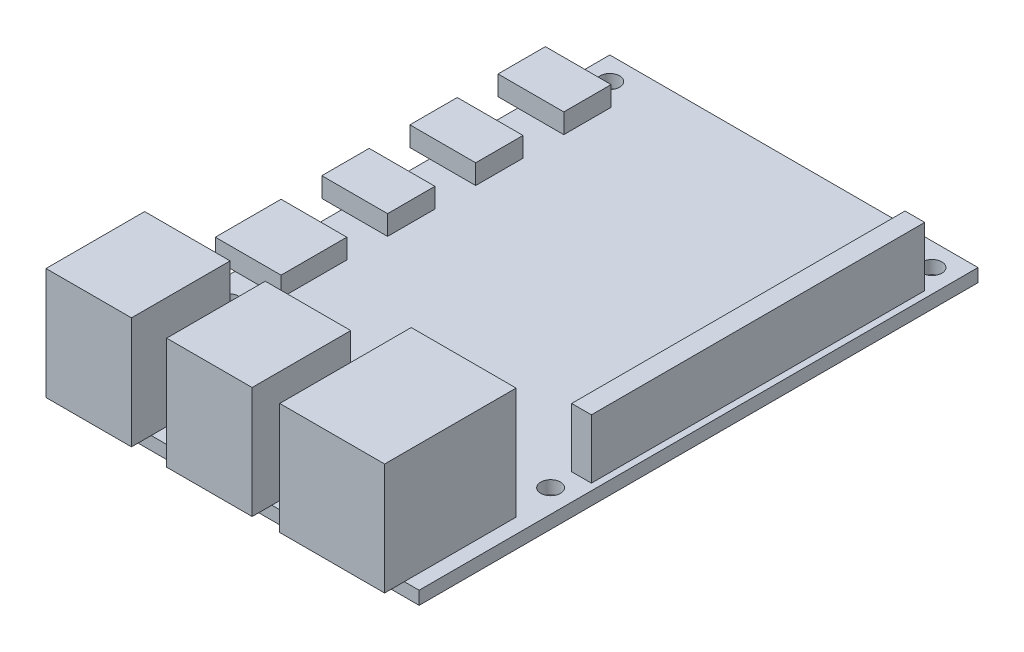
SolidWorks part; units mm, degrees
ref_plane "Front Plane" through (0, 0, 0) normal (0, 0, 1) x (1, 0, 0)
ref_plane "Top Plane" through (0, 0, 0) normal (0, 1, 0) x (1, 0, 0)
ref_plane "Right Plane" through (0, 0, 0) normal (1, 0, 0) x (0, 0, -1)
sketch "Sketch1" plane through (0, 0, 0) normal (0, 1, 0) x (1, 0, 0)
  line L1 (-28, -42.5) -> (28, -42.5)
  line L2 (-28, -42.5) -> (-28, 42.5)
  line L3 (-28, 42.5) -> (28, 42.5)
  line L4 (28, -42.5) -> (28, 42.5)
  line L5 (-28, -42.5) -> (28, 42.5) construction
  line L6 (-28, 42.5) -> (28, -42.5) construction
  line L7 (-24.5, 39) -> (24.5, 39) construction
  line L8 (-24.5, 39) -> (-24.5, -19) construction
  line L9 (-24.5, -19) -> (24.5, -19) construction
  line L10 (24.5, 39) -> (24.5, -19) construction
  circle A0 centre (-24.5, 39) radius 1.5
  circle A1 centre (24.5, 39) radius 1.5
  circle A2 centre (-24.5, -19) radius 1.5
  circle A3 centre (24.5, -19) radius 1.5
  point P0 (0, 0)
  point P10 (0, 39)
  dimension "D6" = 3
  dimension "D1" = 56
  dimension "D2" = 85
  dimension "D3" = 49
  dimension "D4" = 58
  dimension "D5" = 3.5
extrude "Boss-Extrude1" add sketch "Sketch1" along normal blind 2
sketch "Sketch2" plane through (0, 2, 0) normal (0, 1, 0) x (1, 0, 0)
  line L0 (28, 42.5) -> (-28, 42.5) construction
  line L1 (27, 35.4) -> (24, 35.4)
  line L2 (27, 35.4) -> (27, -15.3)
  line L3 (27, -15.3) -> (24, -15.3)
  line L4 (24, 35.4) -> (24, -15.3)
  line L5 (-28, -42.5) -> (28, -42.5) construction
  line L6 (28, -42.5) -> (28, 42.5) construction
  dimension "D1" = 7.1
  dimension "D2" = 27.2
  dimension "D3" = 3
  dimension "D4" = 1
extrude "Boss-Extrude2" add sketch "Sketch2" along normal blind 9
sketch "Sketch3" plane through (0, 2, 0) normal (0, 1, 0) x (1, 0, 0)
  line L0 (28, -42.5) -> (28, 42.5) construction
  line L1 (-25.75, -30.5) -> (-12.75, -30.5)
  line L2 (-25.75, -30.5) -> (-25.75, -45.5)
  line L3 (-25.75, -45.5) -> (-12.75, -45.5)
  line L4 (-12.75, -30.5) -> (-12.75, -45.5)
  line L5 (-7.4, -30.5) -> (5.6, -30.5)
  line L6 (-7.4, -30.5) -> (-7.4, -45.5)
  line L7 (-7.4, -45.5) -> (5.6, -45.5)
  line L8 (5.6, -30.5) -> (5.6, -45.5)
  line L9 (9.8, -25.5) -> (25.75, -25.5)
  line L10 (9.8, -25.5) -> (9.8, -45.5)
  line L11 (9.8, -45.5) -> (25.75, -45.5)
  line L12 (25.75, -25.5) -> (25.75, -45.5)
  line L13 (-28, 42.5) -> (-28, -42.5) construction
  line L14 (-28, -42.5) -> (28, -42.5) construction
  dimension "D1" = 2.25
  dimension "D2" = 2.25
  dimension "D3" = 20.6
  dimension "D4" = 37.8
  dimension "D5" = 13
  dimension "D6" = 15
  dimension "D7" = 20
  dimension "D8" = 3
extrude "Boss-Extrude3" add sketch "Sketch3" along normal blind 17
sketch "Sketch4" plane through (0, 2, 0) normal (0, 1, 0) x (1, 0, 0)
  line L0 (-28, 42.5) -> (-28, -42.5) construction
  line L1 (-31, 35.7) -> (-21, 35.7)
  line L2 (-31, 35.7) -> (-31, 28.5)
  line L3 (-31, 28.5) -> (-21, 28.5)
  line L4 (-21, 35.7) -> (-21, 28.5)
  line L5 (-31, 8.9) -> (-21, 8.9)
  line L6 (-31, 8.9) -> (-31, 1.7)
  line L7 (-31, 1.7) -> (-21, 1.7)
  line L8 (-21, 8.9) -> (-21, 1.7)
  line L9 (-31, -4.5) -> (-21, -4.5)
  line L10 (-31, -4.5) -> (-31, -14.5)
  line L11 (-31, -14.5) -> (-21, -14.5)
  line L12 (-21, -4.5) -> (-21, -14.5)
  line L13 (28, 42.5) -> (-28, 42.5) construction
  line L14 (-31, 28.5) -> (-31, 22.3) construction
  line L15 (-31, 22.3) -> (-21, 22.3)
  line L16 (-31, 22.3) -> (-31, 15.1)
  line L17 (-31, 15.1) -> (-21, 15.1)
  line L18 (-21, 22.3) -> (-21, 15.1)
  line L19 (-31, 15.1) -> (-31, 8.9) construction
  line L20 (-31, 1.7) -> (-31, -4.5) construction
  point P16 (-31, -9.5)
  dimension "D1" = 3
  dimension "D2" = 6.8
  dimension "D3" = 7.2
  dimension "D4" = 11.2
  dimension "D5" = 10
  dimension "D6" = 10
extrude "Boss-Extrude4" add sketch "Sketch4" along normal blind 3
